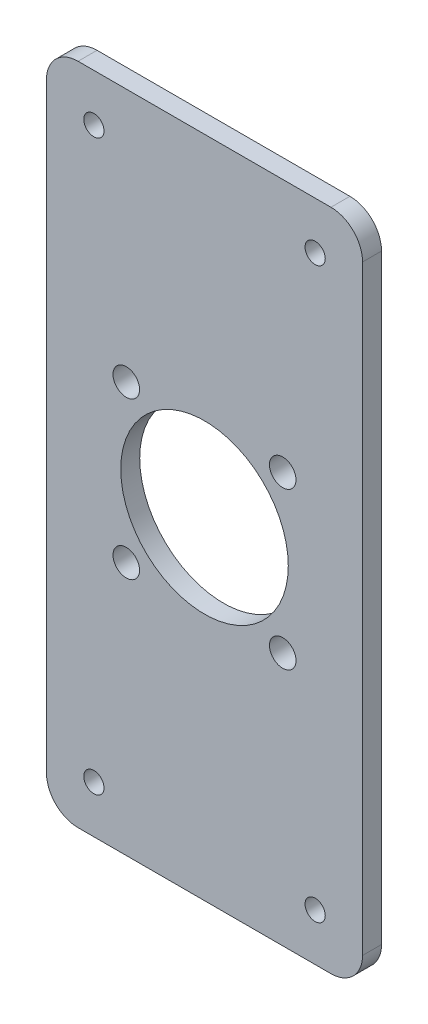
SolidWorks part; units mm, degrees
ref_plane "正面" through (0, 0, 0) normal (0, 0, 1) x (1, 0, 0)
ref_plane "平面" through (0, 0, 0) normal (0, 1, 0) x (1, 0, 0)
ref_plane "右側面" through (0, 0, 0) normal (1, 0, 0) x (0, 0, -1)
sketch "ｽｹｯﾁ2" plane through (0, 0, 0) normal (0, 0, 1) x (1, 0, 0)
  line L0 (25, 105) -> (25, 0) construction
  line L1 (0, 0) -> (50, 0)
  line L2 (0, 0) -> (0, 105)
  line L3 (0, 105) -> (50, 105)
  line L4 (50, 0) -> (50, 105)
  line L5 (7.5, 97.5) -> (42.5, 97.5) construction
  line L6 (7.5, 7.5) -> (42.5, 7.5) construction
  line L7 (12.6256, 40.1256) -> (37.3744, 64.8744) construction
  line L8 (37.3744, 40.1256) -> (12.6256, 64.8744) construction
  circle A0 centre (25, 52.5) radius 13.25
  circle A6 centre (7.5, 97.5) radius 1.6
  circle A7 centre (42.5, 97.5) radius 1.6
  circle A8 centre (42.5, 7.5) radius 1.6
  circle A9 centre (7.5, 7.5) radius 1.6
  circle A10 centre (37.3744, 64.8744) radius 2.1
  circle A11 centre (12.6256, 64.8744) radius 2.1
  circle A12 centre (37.3744, 40.1256) radius 2.1
  circle A13 centre (12.6256, 40.1256) radius 2.1
  point P13 (25, 52.5)
  point P16 (25, 52.5)
  point P21 (25, 97.5)
  point P24 (25, 7.5)
  dimension "D2" = 26.5
  dimension "D3" = 35
  dimension "D4" = 45
  dimension "D6" = 7.5
  dimension "D8" = 7.5
  dimension "D9" = 3.2
  dimension "D10" = 4.2
  dimension "D1" = 90
  dimension "D5" = 50
  dimension "D7" = 7.5
extrude "ﾎﾞｽ - 押し出し1" add sketch "ｽｹｯﾁ2" along normal blind 3
fillet "ﾌｨﾚｯﾄ1" radius 5 4 edges at (0, 0, 1.5) (50, 0, 1.5) (0, 105, 1.5) (50, 105, 1.5)
